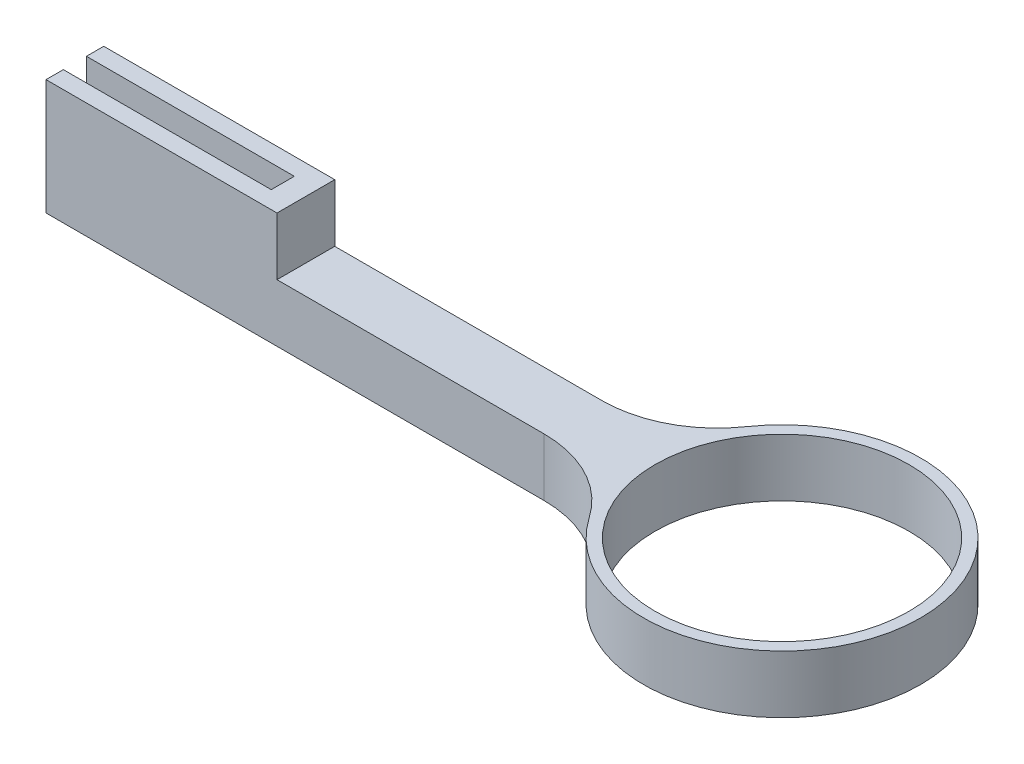
SolidWorks part; units mm, degrees
ref_plane "Спереди" through (0, 0, 0) normal (0, 0, 1) x (1, 0, 0)
ref_plane "Сверху" through (0, 0, 0) normal (0, 1, 0) x (1, 0, 0)
ref_plane "Справа" through (0, 0, 0) normal (1, 0, 0) x (0, 0, -1)
sketch "Эскиз1" plane through (0, 0, 0) normal (0, 1, 0) x (1, 0, 0)
  circle A0 centre (0, 0) radius 11
  circle A1 centre (0, 0) radius 12
  dimension "D1" = 22
  dimension "D2" = 24
extrude "ring" add sketch "Эскиз1" along normal blind 5
sketch "Эскиз2" plane through (0, 0, 0) normal (0, 1, 0) x (1, 0, 0)
  line L0 (34.0214, 0) -> (-42.1067, 0) construction
  line L2 (-11.225, 2.5) -> (-61.225, 2.5)
  line L3 (-11.225, 2.5) -> (-11.225, -2.5)
  line L4 (-11.225, -2.5) -> (-61.225, -2.5)
  line L5 (-61.225, 2.5) -> (-61.225, -2.5)
  circle A0 centre (0, 0) radius 11.5 construction
  dimension "D3" = 23
  dimension "D1" = 2.5
  dimension "D2" = 5
  dimension "D4" = 50
extrude "stick" add sketch "Эскиз2" along normal blind 5
sketch "Эскиз3" plane through (0, 0, 0) normal (0, 1, 0) x (1, 0, 0)
  line L0 (-61.225, -2.5) -> (-11.7367, -2.5) construction
  line L1 (-61.225, 2.5) -> (-41.225, 2.5)
  line L2 (-61.225, 2.5) -> (-61.225, -2.5)
  line L3 (-61.225, -2.5) -> (-41.225, -2.5)
  line L4 (-41.225, 2.5) -> (-41.225, -2.5)
  dimension "D1" = 20
extrude "key" add sketch "Эскиз3" along normal blind 10
sketch "Эскиз5" plane through (-61.225, 0, 0) normal (-1, 0, 0) x (0, 0, 1)
  line L0 (-2.5, 10) -> (2.5, 10) construction
  line L1 (-1, 10) -> (1, 10)
  line L2 (-1, 10) -> (-1, 5)
  line L3 (-1, 5) -> (1, 5)
  line L4 (1, 10) -> (1, 5)
  line L5 (-2.5, 5) -> (2.5, 5) construction
  dimension "D2" = 2
  dimension "D3" = 1.5
fillet "Скругление1" radius 10 2 edges at (-11.7367, 2.5, 2.5) (-11.7367, 2.5, -2.5)
extrude "slot" cut sketch "Эскиз5" against normal blind 18
